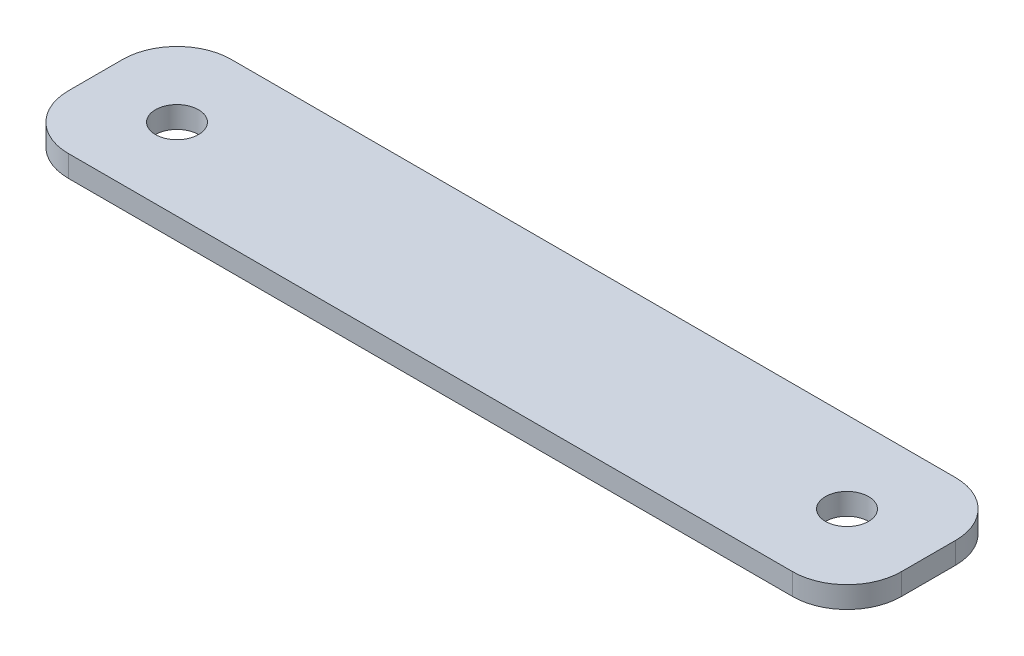
SolidWorks part; units mm, degrees
ref_plane "Front Plane" through (0, 0, 0) normal (0, 0, 1) x (1, 0, 0)
ref_plane "Top Plane" through (0, 0, 0) normal (0, 1, 0) x (1, 0, 0)
ref_plane "Right Plane" through (0, 0, 0) normal (1, 0, 0) x (0, 0, -1)
sketch "Sketch1" plane through (0, 0, 0) normal (0, 1, 0) x (1, 0, 0)
  line L0 (-24.672, 0) -> (24.672, 0) construction
  line L1 (30.672, -6) -> (-30.672, -6)
  line L2 (30.672, -6) -> (30.672, 6)
  line L3 (30.672, 6) -> (-30.672, 6)
  line L4 (-30.672, -6) -> (-30.672, 6)
  line L5 (30.672, -6) -> (-30.672, 6) construction
  line L6 (30.672, 6) -> (-30.672, -6) construction
  circle A0 centre (-24.672, 0) radius 1.5875
  circle A1 centre (24.672, 0) radius 1.5875
  circle A2 centre (-24.672, 0) radius 5 construction
  point P0 (0, 0)
  point P8 (0, 0)
  dimension "D1" = 3.175
  dimension "D4" = 10
  dimension "D2" = 49.344
  dimension "D3" = 12
  dimension "D5" = 6
extrude "Boss-Extrude1" add sketch "Sketch1" along normal mid plane 1.5875
fillet "Fillet1" radius 4 4 edges at (-30.672, 0, 6) (-30.672, 0, -6) (30.672, 0, 6) (30.672, 0, -6)
